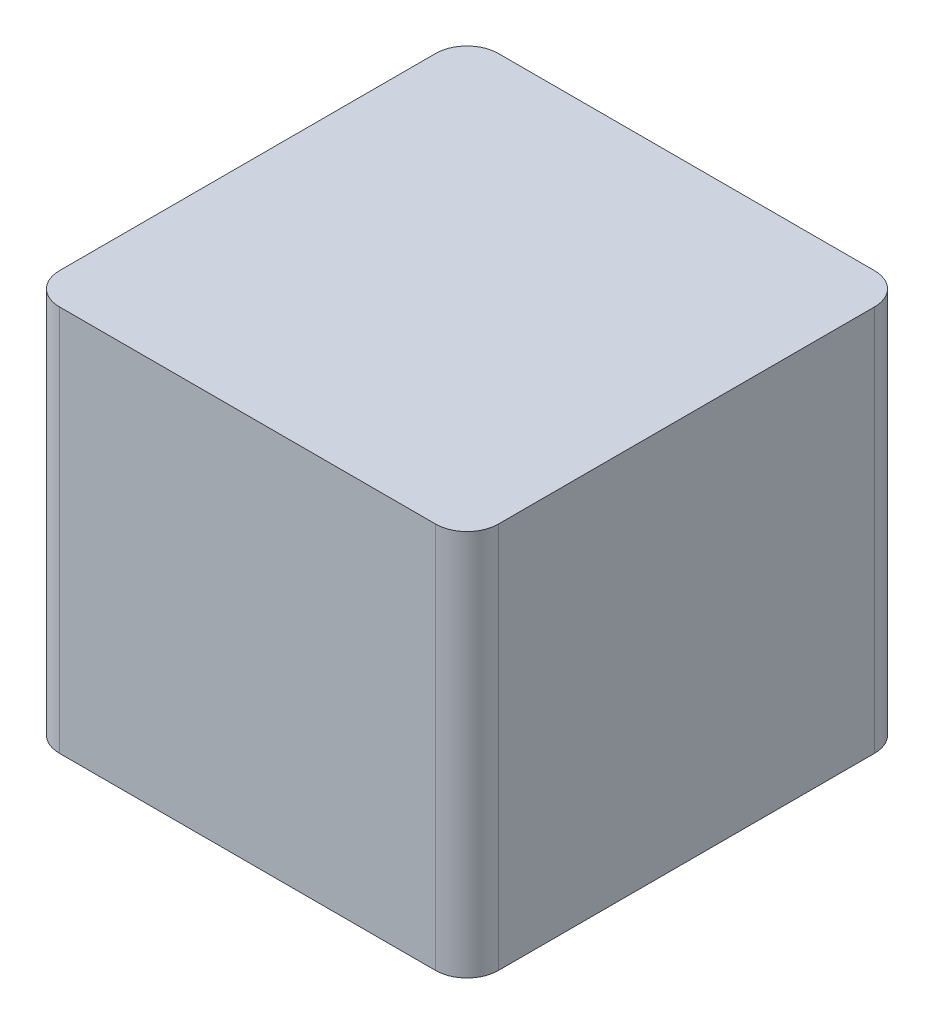
SolidWorks part; units mm, degrees
ref_plane "前视基准面" through (0, 0, 0) normal (0, 0, 1) x (1, 0, 0)
ref_plane "上视基准面" through (0, 0, 0) normal (0, 1, 0) x (1, 0, 0)
ref_plane "右视基准面" through (0, 0, 0) normal (1, 0, 0) x (0, 0, -1)
other "Configuration Table"
sketch "草图1" plane through (0, 0, 0) normal (0, 0, 1) x (1, 0, 0)
  line L0 (0, 0) -> (42, 0)
  line L1 (42, 0) -> (42, 37)
  line L2 (42, 37) -> (0, 37)
  line L3 (0, 37) -> (0, 0)
  dimension "width" = 42
  dimension "height" = 37
extrude "BlockExtrude" add sketch "草图1" along normal blind 42
fillet "Fillet" radius 3 4 edges at (0, 18.5, 0) (42, 18.5, 0) (0, 18.5, 42) (42, 18.5, 42) tangent propagation no
